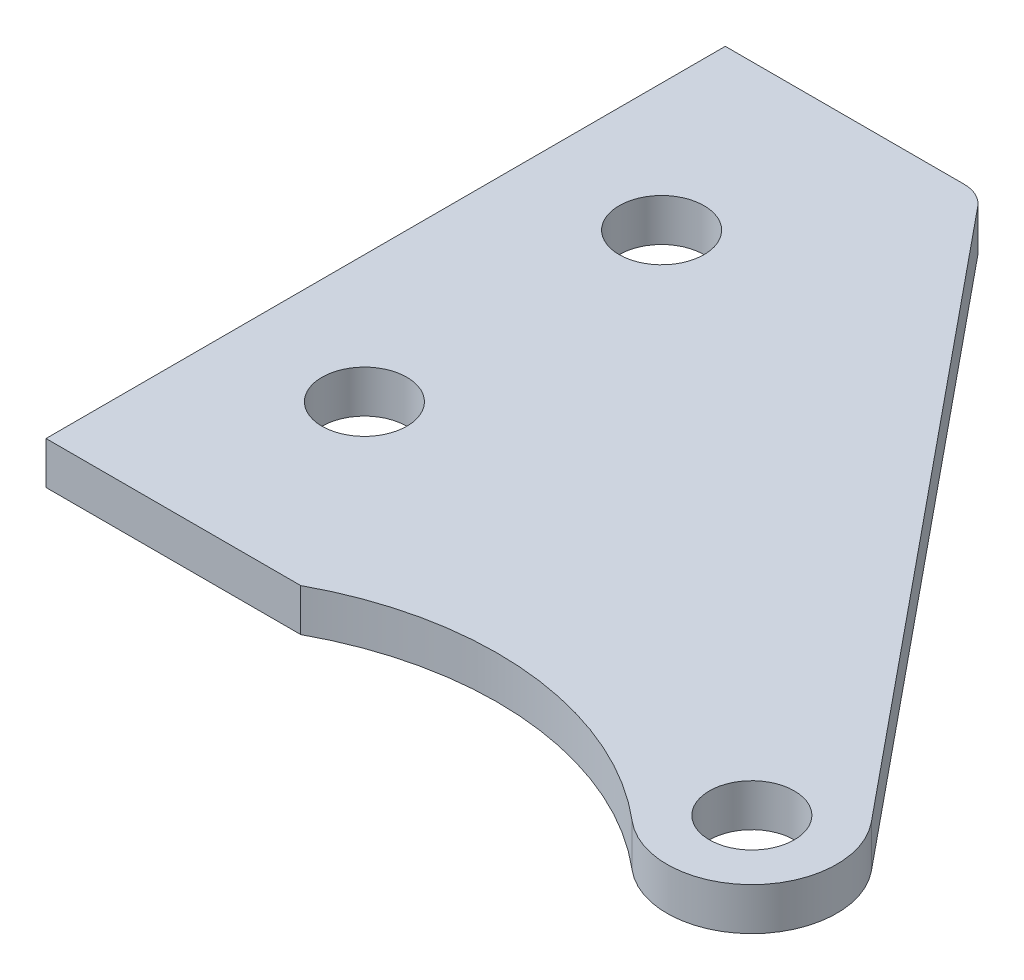
SolidWorks part; units mm, degrees
material "6061-T6 (SS)"
ref_plane "Front" through (0, 0, 0) normal (0, 0, 1) x (1, 0, 0)
ref_plane "Top" through (0, 0, 0) normal (0, 1, 0) x (1, 0, 0)
ref_plane "Right" through (0, 0, 0) normal (1, 0, 0) x (0, 0, -1)
sketch "Sketch1" plane through (0, 0, 0) normal (0, 1, 0) x (1, 0, 0)
  line L1 (0, 50.8) -> (19.05, 50.8)
  line L3 (19.05, 50.8) -> (55.7137, 6.0089)
  line L4 (0, 50.8) -> (0, 0)
  line L6 (0, 0) -> (19.05, 0)
  arc A0 (55.7137, 6.0089) -> (46.6945, -2.8575) centre (50.8, 1.9868) cw
  arc A3 (19.05, 0) -> (46.6945, -2.8575) centre (30.784, -21.6311) cw
  point P2 (26.8146, -1.9483)
  point P7 (0, 0)
  point P10 (0, 0)
  point P11 (19.05, 0)
  point P12 (0, 0)
  dimension "D1" = 19.05
  dimension "D3" = 6.35
  dimension "D4" = 50.8
  dimension "D5" = 50.8
extrude "Boss-Extrude1" add sketch "Sketch1" along normal blind 3.175
hole_wizard "1/4 (0.25) Diameter Hole2" positions "Sketch4" profile "Sketch3" hole size "1/4" standard "ANSI Inch" end condition through all
sketch "Sketch4" plane through (0, 0, 0) normal (0, -1, 0) x (-1, 0, 0)
  point P0 (-50.8, 1.9868)
sketch "Sketch3" plane through (50.8, 0, -1.9868) normal (1, 0, 0) x (0, 0, -1)
  line L0 (0, 0) -> (0, 3.175)
  line L1 (0, 3.175) -> (3.175, 3.175)
  line L2 (3.175, 3.175) -> (3.175, 0)
  line L5 (3.175, 0) -> (0, 0)
  line L11 (0, -6.35) -> (0, 107.95) construction
  dimension "Thru Hole Dia." = 6.35
  dimension "Thru Hole Depth" = 3.175
hole_wizard "1/4 (0.25) Diameter Hole1" positions "Sketch7" profile "Sketch8" hole size "1/4" standard "ANSI Inch" end condition through all
sketch "Sketch7" plane through (0, 3.175, 0) normal (0, 1, 0) x (1, 0, 0)
  line L9 (9.525, 0) -> (9.525, 14.2875) construction
  line L10 (0, 0) -> (19.05, 0) construction
  line L11 (9.525, 14.2875) -> (9.525, 36.5125) construction
  line L12 (9.525, 36.5125) -> (9.525, 50.8) construction
  line L13 (19.05, 50.8) -> (0, 50.8) construction
  point P0 (9.525, 36.5125)
  point P2 (9.525, 14.2875)
  dimension "D1" = 22.225
sketch "Sketch8" plane through (9.525, 3.175, -36.5125) normal (1, 0, 0) x (0, 0, 1)
  line L0 (0, 0) -> (0, 3.175)
  line L1 (0, 3.175) -> (3.175, 3.175)
  line L2 (3.175, 3.175) -> (3.175, 0)
  line L5 (3.175, 0) -> (0, 0)
  line L11 (0, -6.35) -> (0, 107.95) construction
  dimension "Thru Hole Dia." = 6.35
  dimension "Thru Hole Depth" = 3.175
fillet "Fillet1" radius 2.54 1 edges at (19.05, 1.5875, -50.8)
